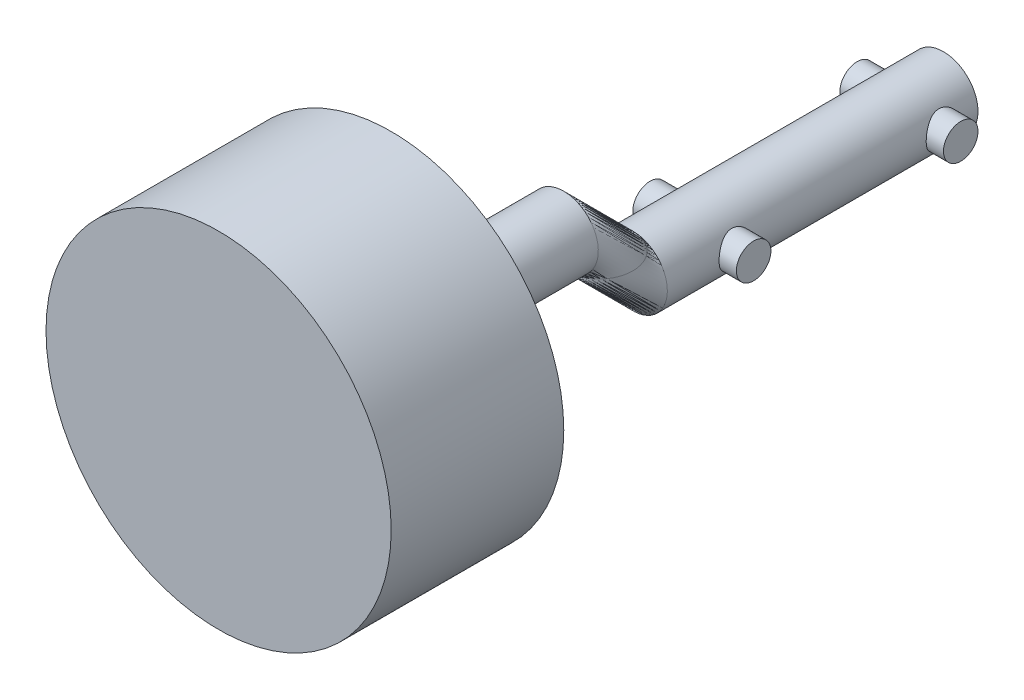
SolidWorks part; units mm, degrees
material "Acier non allié"
ref_plane "Plan de face" through (0, 0, 0) normal (0, 0, 1) x (1, 0, 0)
ref_plane "Plan de dessus" through (0, 0, 0) normal (0, 1, 0) x (1, 0, 0)
ref_plane "Plan de droite" through (0, 0, 0) normal (1, 0, 0) x (0, 0, -1)
sketch "Esquisse1" plane through (0, 0, 0) normal (0, 0, 1) x (1, 0, 0)
  circle A0 centre (0, 0) radius 10
  dimension "D1" = 20
extrude "Boss.-Extru.1" add sketch "Esquisse1" along normal blind 10
sketch "Esquisse2" plane through (0, 0, 0) normal (0, 0, -1) x (-1, 0, 0)
  circle A0 centre (0, 0) radius 2
  dimension "D1" = 4
sketch "Esquisse3" plane through (0, 0, 0) normal (1, 0, 0) x (0, 0, -1)
  line L0 (0, 0) -> (10, 0)
  line L1 (14, -4) -> (32, -4)
  line L2 (10, -2) -> (21.167, -2) construction
  arc A0 (10, 0) -> (12, -2) centre (10, -2) cw
  arc A1 (12, -2) -> (14, -4) centre (14, -2) ccw
  dimension "D2" = 2
  dimension "D3" = 2
  dimension "D1" = 10
  dimension "D4" = 18
sweep "Balayage1" add profiles "Esquisse2" path "Esquisse3"
sketch "Esquisse4" plane through (0, 0, 0) normal (1, 0, 0) x (0, 0, -1)
  line L0 (12.7428, -4) -> (30.7185, -4) construction
  line L1 (32, -6) -> (32, -2) construction
  circle A0 centre (18, -4) radius 1
  circle A1 centre (30, -4) radius 1
  dimension "D1" = 2
  dimension "D2" = 2
  dimension "D3" = 4
  dimension "D4" = 12
  dimension "D5" = 2
extrude "Boss.-Extru.2" add sketch "Esquisse4" along normal blind 3 and the other way blind 3
